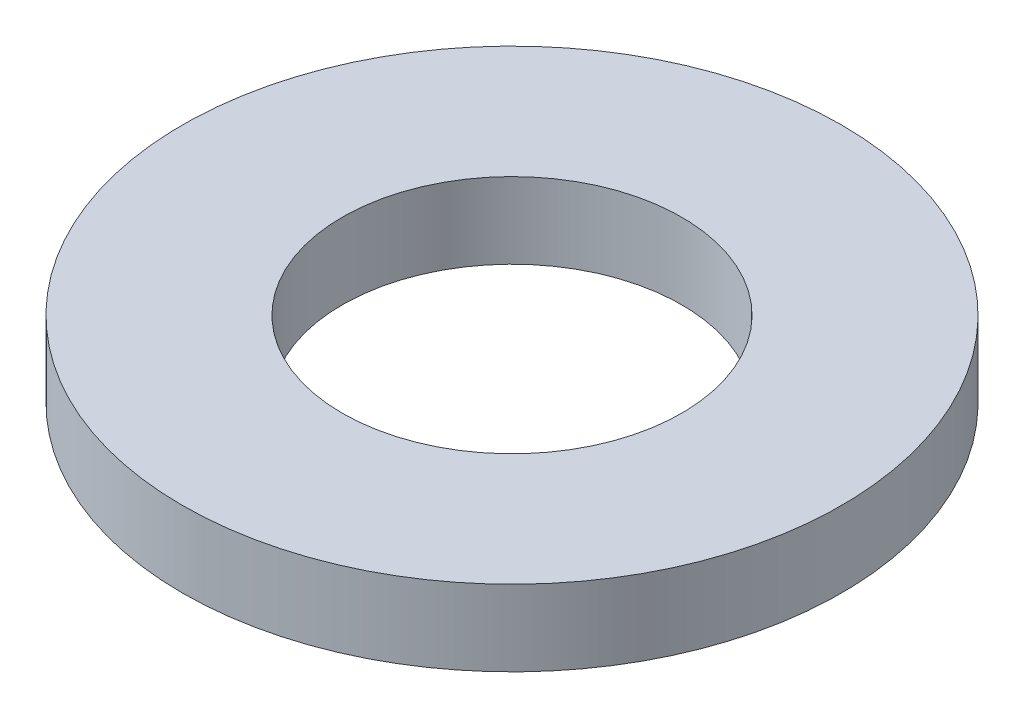
SolidWorks part; units mm, degrees
ref_plane "Front Plane" through (0, 0, 0) normal (0, 0, 1) x (1, 0, 0)
ref_plane "Top Plane" through (0, 0, 0) normal (0, 1, 0) x (1, 0, 0)
ref_plane "Right Plane" through (0, 0, 0) normal (1, 0, 0) x (0, 0, -1)
sketch "Sketch1" plane through (0, 0, 0) normal (0, 1, 0) x (1, 0, 0)
  circle A0 centre (0, 0) radius 82.5
  dimension "FLANGE_OD" = 165
extrude "Boss-Extrude1" add sketch "Sketch1" along normal blind 19
sketch "Sketch2" plane through (0, 0, 0) normal (0, 1, 0) x (1, 0, 0)
  circle A0 centre (0, 0) radius 42.5
  dimension "BORE_D" = 85
extrude "Cut-Extrude1" cut sketch "Sketch2" along normal through all
sketch "Sketch3" plane through (0, 19, 0) normal (0, 1, 0) x (1, 0, 0)
  circle A0 centre (0, 0) radius 35.1652 construction
  circle A1 centre (-35.1652, 0) radius 6.4637
  dimension "BOLT_D" = 12.9275
  dimension "BOLT_PCD" = 70.3304
extrude "Cut-Extrude2" cut sketch "Sketch3" against normal blind 15.7852 rebuild error yes
pattern_circular "CirPattern1" count 3 over 360 rebuild error yes
